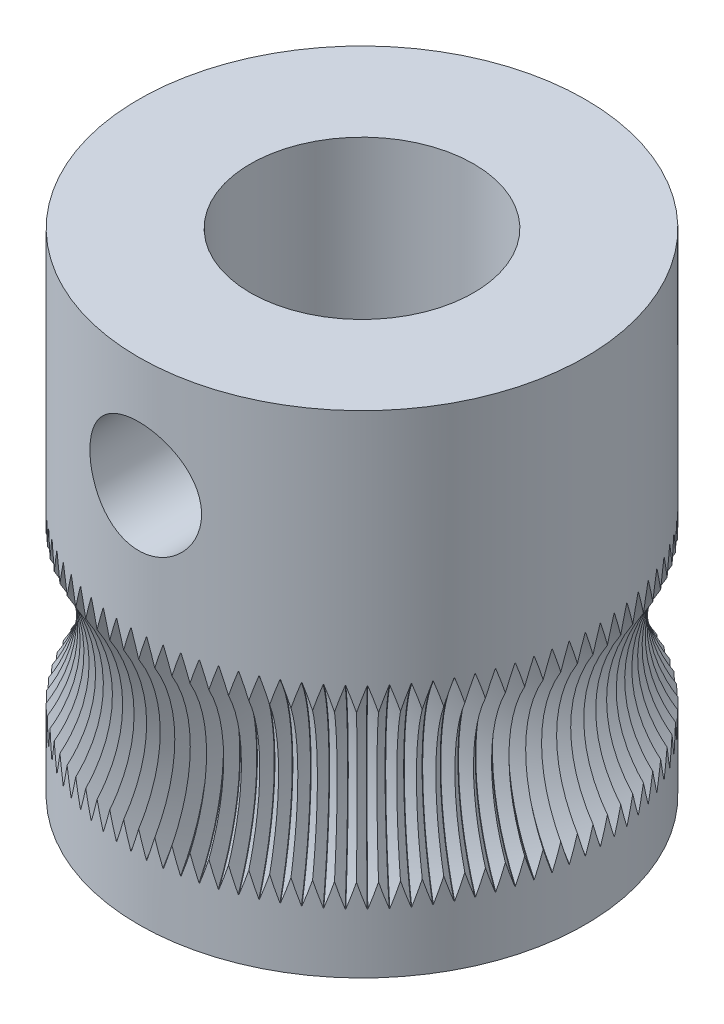
SolidWorks part; units mm, degrees
ref_plane "Front Plane" through (0, 0, 0) normal (0, 0, 1) x (1, 0, 0)
ref_plane "Top Plane" through (0, 0, 0) normal (0, 1, 0) x (1, 0, 0)
ref_plane "Right Plane" through (0, 0, 0) normal (1, 0, 0) x (0, 0, -1)
sketch "Sketch1" plane through (0, 0, 0) normal (0, 1, 0) x (1, 0, 0)
  circle A0 centre (0, 0) radius 5
  circle A1 centre (0, 0) radius 2.5
  dimension "D1" = 10
  dimension "D2" = 5
extrude "Boss-Extrude1" add sketch "Sketch1" along normal blind 11
ref_plane "Plane1" through (0, 0, 5) normal (0, 0, 1) x (1, 0, 0)
ref_axis "Axis1" through (0, 11, 0) along (0, -1, 0)
hole_wizard "M3 Tapped Hole1" positions "Sketch6" profile "Sketch7" tap size "M3" standard "ISO" end condition up to next
sketch "Sketch6" plane through (0, 0, 5) normal (0, 0, 1) x (1, 0, 0)
  line L0 (5, 11) -> (-5, 11) construction
  line L1 (0, 11) -> (0, 0) construction
  point P1 (0, 8.5)
  dimension "D1" = 2.5
cosmetic thread "Hole Thread1" parameters "D2"=3
sketch "Sketch7" plane through (0, 8.5, 5) normal (1, 0, 0) x (0, -1, 0)
  line L0 (0, 0) -> (0, 2.5)
  line L1 (0, 2.5) -> (1.25, 2.5)
  line L2 (1.25, 2.5) -> (1.25, 0)
  line L5 (1.25, 0) -> (0, 0)
  line L11 (0, -6.35) -> (0, 107.95) construction
  dimension "Thru Tap Drill Dia." = 2.5
  dimension "Thru Tap Drill Depth" = 2.5
ref_plane "Plane3" through (0, 0, 0) normal (0, 0, 1) x (1, 0, 0)
sketch "Sketch8" plane through (0, 0, 0) normal (0, 0, 1) x (1, 0, 0)
  line L0 (0, 11) -> (0, 0) construction
  line L1 (5, 11) -> (-5, 11) construction
  line L2 (7.75, 3.5) -> (7.75, 8.3641) construction
  circle A0 centre (7.75, 3.5) radius 3.5
  point P6 (7.75, 7)
  dimension "D1" = 7
  dimension "D2" = 7.75
  dimension "D3" = 7.5
ref_plane "Plane4" through (7.75, 0, 0) normal (1, 0, 0) x (0, 0, -1)
sketch "Sketch10" plane through (7.75, 0, 0) normal (1, 0, 0) x (0, 0, -1)
  line L0 (-0.9697, 5.3292) -> (0.9697, 5.3292)
  line L1 (0.9697, 5.3292) -> (0.005, 7)
  line L2 (0.005, 7) -> (-0.005, 7)
  line L3 (-0.005, 7) -> (-0.9697, 5.3292)
  line L6 (0, 3.5) -> (0, 8.3641) construction
  point P2 (0, 7)
  point P5 (0, 5.3292)
  dimension "D1" = 0.01
  dimension "D2" = 60
sweep "Cut-Sweep1" cut profiles "Sketch10" path "Sketch8"
pattern_circular "CirPattern1" count 90 every 4 about axis through (0, 11, 0) along (0, -1, 0) of "Cut-Sweep1"
